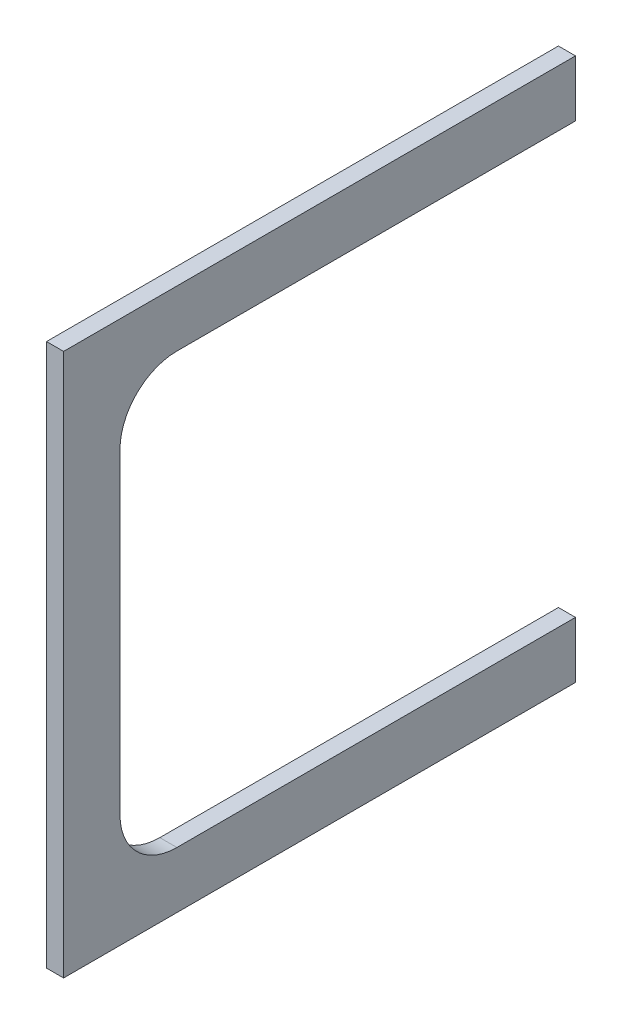
SolidWorks part; units mm, degrees
ref_plane "Спереди" through (0, 0, 0) normal (0, 0, 1) x (1, 0, 0)
ref_plane "Сверху" through (0, 0, 0) normal (0, 1, 0) x (1, 0, 0)
ref_plane "Справа" through (0, 0, 0) normal (1, 0, 0) x (0, 0, -1)
ref_plane "Плоскость4" through (-1.5, 0, 0) normal (-1, 0, 0) x (0, -1, 0)
sketch "Эскиз1" plane through (-1.5, 0, 0) normal (-1, 0, 0) x (0, -1, 0)
  line L0 (-237, -36.5) -> (-237, 33.5)
  line L1 (-227, 43.5) -> (-171.5, 43.5)
  line L2 (-161.5, 33.5) -> (-161.5, -36.5)
  line L3 (-161.5, -36.5) -> (-151.6, -36.5)
  line L4 (-151.6, -36.5) -> (-151.6, 53.4)
  line L5 (-151.6, 53.4) -> (-246.9, 53.4)
  line L6 (-246.9, 53.4) -> (-246.9, -36.5)
  line L7 (-246.9, -36.5) -> (-237, -36.5)
  arc A0 (-237, 33.5) -> (-227, 43.5) centre (-227, 33.5) cw
  arc A1 (-171.5, 43.5) -> (-161.5, 33.5) centre (-171.5, 33.5) cw
extrude "Бобышка-Вытянуть1" add sketch "Эскиз1" against normal blind 3
ref_axis "Ось1" through (0, 151.6, 53.4) along (0, 1, 0)
